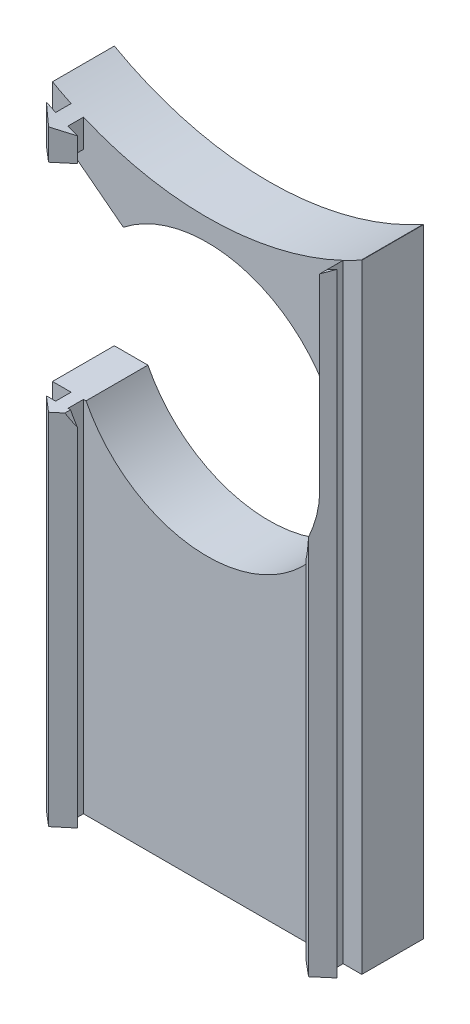
SolidWorks part; units mm, degrees
ref_plane "Alzado" through (0, 0, 0) normal (0, 0, 1) x (1, 0, 0)
ref_plane "Planta" through (0, 0, 0) normal (0, 1, 0) x (1, 0, 0)
ref_plane "Vista lateral" through (0, 0, 0) normal (1, 0, 0) x (0, 0, -1)
sketch "Croquis1" plane through (0, 0, 0) normal (0, 1, 0) x (1, 0, 0)
  line L0 (-25, 0) -> (25, 0)
  line L8 (-25, 0) -> (-25, -10)
  line L15 (-25, -10) -> (-21.9906, -10)
  line L16 (-23.4906, -12.5) -> (-21.9906, -12.5)
  line L17 (-19.9906, -10) -> (-19.9906, -12.5)
  line L18 (-21.9906, -10) -> (-21.9906, -12.5)
  line L19 (-19.9906, -12.5) -> (-18.4906, -12.5)
  line L20 (-23.4906, -12.5) -> (-21.014, -14.6191)
  line L21 (-21.014, -14.6191) -> (-18.4906, -12.5)
  line L22 (-19.9906, -10) -> (-17, -10)
  line L23 (0, 0) -> (0, -14.6191) construction
  line L24 (19.9906, -10) -> (17, -10)
  line L25 (21.014, -14.6191) -> (18.4906, -12.5)
  line L26 (23.4906, -12.5) -> (21.014, -14.6191)
  line L27 (19.9906, -12.5) -> (18.4906, -12.5)
  line L28 (21.9906, -10) -> (21.9906, -12.5)
  line L29 (19.9906, -10) -> (19.9906, -12.5)
  line L30 (23.4906, -12.5) -> (21.9906, -12.5)
  line L31 (25, -10) -> (21.9906, -10)
  line L33 (25, 0) -> (25, -10)
  line L34 (17, -10) -> (-17, -10)
  point P10 (0, -5.8984)
  point P11 (-20.9906, -10.0474)
  point P30 (20.9906, -10.0474)
  dimension "D1" = 8
  dimension "D2" = 25
  dimension "D3" = 10
  dimension "D4" = 5
  dimension "D5" = 1.5
  dimension "D6" = 2.5
  dimension "D7" = 2.5
  dimension "D8" = 1.5
  dimension "D9" = 40.024
extrude "Saliente-Extruir1" add sketch "Croquis1" along normal blind 100
sketch "Croquis2" plane through (0, 0, 0) normal (0, 0, -1) x (-1, 0, 0)
  circle A0 centre (0, 68.0235) radius 21.9851
extrude "Cortar-Extruir1" cut sketch "Croquis2" against normal blind 19
sketch "Croquis3" plane through (0, 0, 0) normal (0, 0, -1) x (-1, 0, 0)
  line L1 (-13.8982, 78.0235) -> (31.7204, 78.0235)
  line L2 (-13.8982, 78.0235) -> (-13.8982, 58.0235)
  line L3 (-13.8982, 58.0235) -> (31.7204, 58.0235)
  line L4 (31.7204, 78.0235) -> (31.7204, 58.0235)
  line L5 (-13.8982, 78.0235) -> (31.7204, 58.0235) construction
  line L6 (-13.8982, 58.0235) -> (31.7204, 78.0235) construction
  point P0 (8.9111, 68.0235)
  dimension "D1" = 20
extrude "Cortar-Extruir2" cut sketch "Croquis3" against normal blind 19
sketch "Croquis5" plane through (0, 78.0235, 0) normal (0, -1, 0) x (1, 0, 0)
  line L1 (-17.0279, 19.2383) -> (-25, 19.2383)
  line L2 (-17.0279, 19.2383) -> (-17.0279, 10)
  line L3 (-17.0279, 10) -> (-25, 10)
  line L4 (-25, 19.2383) -> (-25, 10)
  line L5 (-17.0279, 19.2383) -> (-25, 10) construction
  line L6 (-17.0279, 10) -> (-25, 19.2383) construction
  point P0 (-21.014, 14.6191)
extrude "Cortar-Extruir3" cut sketch "Croquis5" against normal blind 15
sketch "Croquis6" plane through (0, 0, 0) normal (0, 0, -1) x (-1, 0, 0)
  arc A0 (-24.9388, 100) -> (25.0182, 100) centre (0.0397, 144.6878) ccw
  arc A3 (-24.9388, 100) -> (25.0182, 100) centre (0.0397, 96.0572) cw
  point P7 (25.5755, 100)
  point P11 (-24.9388, 100)
  point P15 (25.0182, 100)
extrude "Cortar-Extruir4" cut sketch "Croquis6" against normal blind 28
sketch "Croquis7" plane through (0, 0, 0) normal (0, 0, -1) x (-1, 0, 0)
  line L0 (25, 94.1477) -> (13.5486, 85.3377)
  line L7 (25, 78.0235) -> (25, 99.9898)
  line L8 (-24.9388, 100) -> (-25, 100)
  line L9 (-25, 100) -> (-25, 0)
  line L10 (-25, 0) -> (25, 0)
  line L11 (25, 0) -> (25, 58.0235)
  line L12 (25, 58.0235) -> (19.5792, 58.0235)
  line L13 (19.5792, 78.0235) -> (25, 78.0235)
  line L14 (25, 78.0235) -> (25, 94.1477)
  line L15 (-24.9388, 100) -> (-25, 100)
  line L20 (19.5792, 78.0235) -> (25, 78.0235)
  arc A2 (-24.9388, 100) -> (25, 99.9898) centre (0.0397, 144.6878) ccw
  arc A3 (19.5792, 78.0235) -> (19.5792, 58.0235) centre (0, 68.0235) ccw
  arc A5 (19.5792, 78.0235) -> (13.5486, 85.3377) centre (0, 68.0235) ccw
  line M10 (25, 78.0235) -> (25, 99.9898)
  arc M17 (19.5792, 58.0235) -> (19.5792, 78.0235) centre (0, 68.0235) cw
  line M18 (19.5792, 78.0235) -> (25, 78.0235)
  dimension "D1" = 0
extrude "Cortar-Extruir5" cut sketch "Croquis7" against normal blind 10 contours L0 M10 M17 M18 region at (-20.988, 84.9787, 0)
ref_plane "Plano3" through (0, 0, 14.6191) normal (0, 0, 1) x (0, -1, 0)
sketch "Croquis11" plane through (0, 0, 14.6191) normal (0, 0, 1) x (0, -1, 0)
  line L0 (-68.0235, 21.9851) -> (-101.2129, 21.9851)
  line L1 (-101.2129, 21.9851) -> (-98.8059, 16.9025)
  line L2 (-98.8059, 16.9025) -> (-68.0235, 16.9025)
  line L3 (-68.0235, 16.9025) -> (-68.0235, 21.9851)
  arc A0 (-61.5615, 21.014) -> (-74.4855, 21.014) centre (-68.0235, 0) ccw construction
extrude "Cortar-Extruir7" cut sketch "Croquis11" against normal up to surface (4.6191 mm away) up to face at (23.7865, 59.6903, 10)
